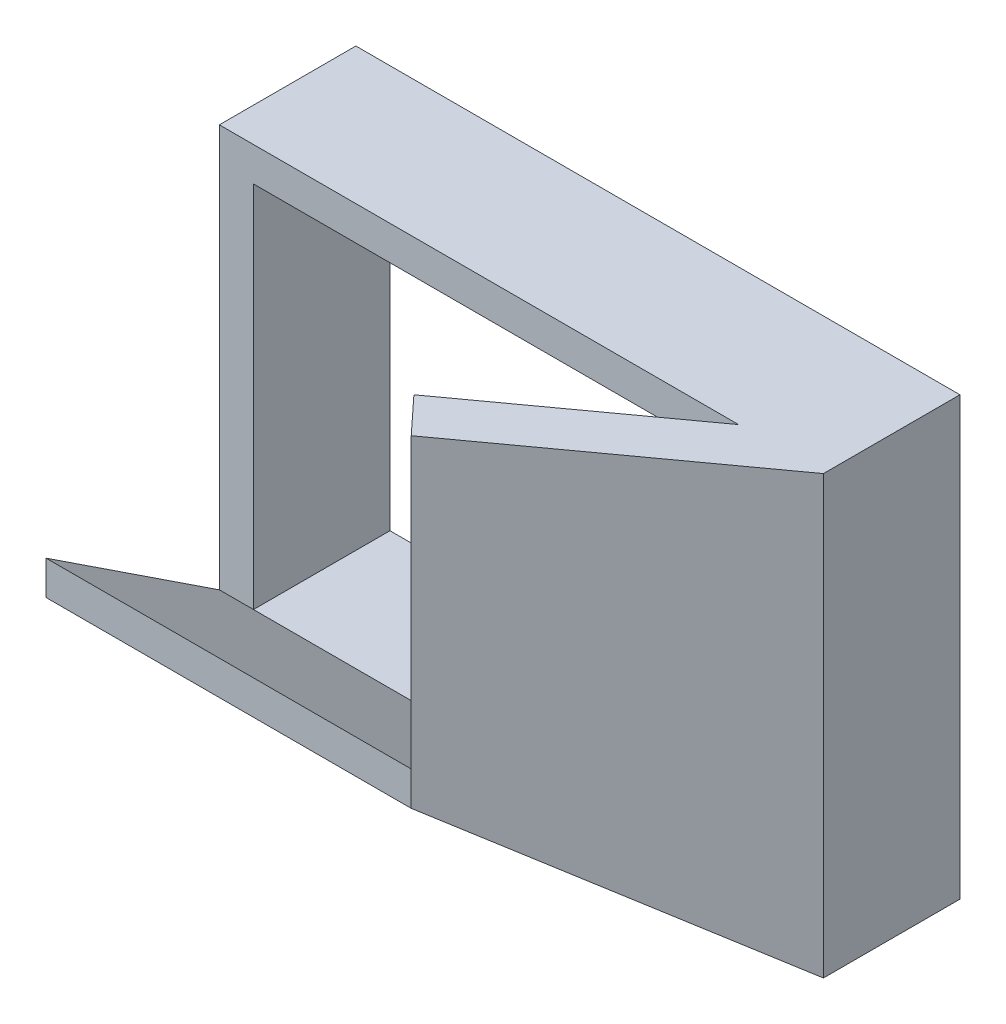
SolidWorks part; units mm, degrees
note: The reader was unsure of these and kept them because the rebuilt part matched: shared geometry of "Sketch11<3>".
ref_plane "Front Plane" through (0, 0, 0) normal (0, 0, 1) x (1, 0, 0)
ref_plane "Top Plane" through (0, 0, 0) normal (0, 1, 0) x (1, 0, 0)
ref_plane "Right Plane" through (0, 0, 0) normal (1, 0, 0) x (0, 0, -1)
sketch "Sketch1" plane through (0, 0, 0) normal (0, 0, 1) x (1, 0, 0)
  line L1 (-26.4, -1.3) -> (-8.7, -1.3)
  line L2 (-26.4, -1.3) -> (-26.4, -14.1)
  line L3 (-26.4, -14.1) -> (-8.7, -14.1)
  line L4 (-8.7, -1.3) -> (-8.7, -14.1)
  line L5 (-7.5, -15) -> (-27.5, -15)
  line L6 (-7.5, -15) -> (-7.5, 0)
  line L7 (-7.5, 0) -> (-27.5, 0)
  line L8 (-27.5, -15) -> (-27.5, 0)
  line L10 (-25.4, -2.3) -> (-9.7, -2.3)
  line L11 (-25.4, -2.3) -> (-25.4, -13.1)
  line L12 (-25.4, -13.1) -> (-9.7, -13.1)
  line L13 (-9.7, -2.3) -> (-9.7, -13.1)
  line L14 (-6.5, 0) -> (-28.5, 0)
  line L15 (-6.5, 0) -> (-6.5, -16)
  line L16 (-6.5, -16) -> (-28.5, -16)
  line L17 (-28.5, 0) -> (-28.5, -16)
  dimension "D1" = 1
  dimension "D2" = 1
  dimension "D3" = 1
  dimension "D4" = 17.7
  dimension "D5" = 0
  dimension "D6" = 1
  dimension "D7" = 1
  dimension "D8" = 1
  dimension "D9" = 1
  dimension "D10" = 12.8
extrude "Boss-Extrude1" add sketch "Sketch1" against normal blind 4 contours L4 L1 L2 L3 L10 L13 L12 L11
sketch "Sketch7" plane through (0, -14.1, 0) normal (0, -1, 0) x (1, 0, 0)
  line L0 (-8.7, 0) -> (-15.7, 5.0777)
  line L1 (-15.7, 5.0777) -> (-16.7, 4)
  line L2 (-16.7, 4) -> (-9.7, -1.0777)
  line L3 (-9.7, -1.0777) -> (-9.7, 1.4618)
  line L4 (-26.4, 0) -> (-8.7, 0) construction
  line L5 (-8.7, 0) -> (-9.7, -1.0777)
  dimension "D1" = 1
  dimension "D2" = 4
  dimension "D3" = 8
extrude "Boss-Extrude2" add sketch "Sketch7" against normal up to surface (12.8 mm away)
sketch "Sketch11" plane through (-8.7, 0, -8.7) normal (1, 0, 0) x (0, 0, 1)
  line L3 (8.7, 13.1) -> (8.7, 14.1)
  line L4 (8.7, 1.3) -> (8.7, 14.1) construction
  line L6 (4.7, 14.1) -> (8.7, 14.1) construction
  line L8 (8.7, 14.1) -> (13.7777, 10.7569)
  line L9 (13.7777, 10.7569) -> (13.7777, 9.7569)
  line L10 (13.7777, 9.7569) -> (8.7, 13.1)
  line L11 (13.7777, 1.3) -> (13.7777, 14.1) construction
  dimension "D1" = 1
  dimension "D2" = 1
  dimension "D3" = 0
  dimension "D4" = 0
extrude "Boss-Extrude3" add sketch "Sketch11" against normal up to surface (17.7 mm away) up to face at (-26.4, -7.7, -2)
sketch "Sketch13" plane through (-8.7, 0, 0) normal (1, 0, 0) x (0, 0, -1)
  line L6 (-5.0777, -10.7569) -> (-5.0777, -15.2959)
  line L7 (-5.0777, -15.2959) -> (0, -14.1)
  line L8 (0, -14.1) -> (-5.0777, -10.7569)
extrude "Cut-Extrude1" cut sketch "Sketch13" against normal through all
sketch "Sketch14" plane through (0, -9.1387, 6.0167) normal (0, 0.8352, -0.5499) x (1, 0, 0)
  line L0 (-8.7, 7.2037) -> (-15.7, 1.1242)
  line L1 (-15.7, 1.1242) -> (-8.7, 1.1242)
  line L2 (-8.7, 1.1242) -> (-8.7, 7.2037)
extrude "Cut-Extrude3" cut sketch "Sketch11<3>" against normal up to surface (7 mm away) up to face at (-12.2, -6.3642, 2.5389)
sketch "Sketch11<3>" plane through (-8.7, 0, -8.7) normal (1, 0, 0) x (0, 0, 1) same geometry as "Sketch11"
